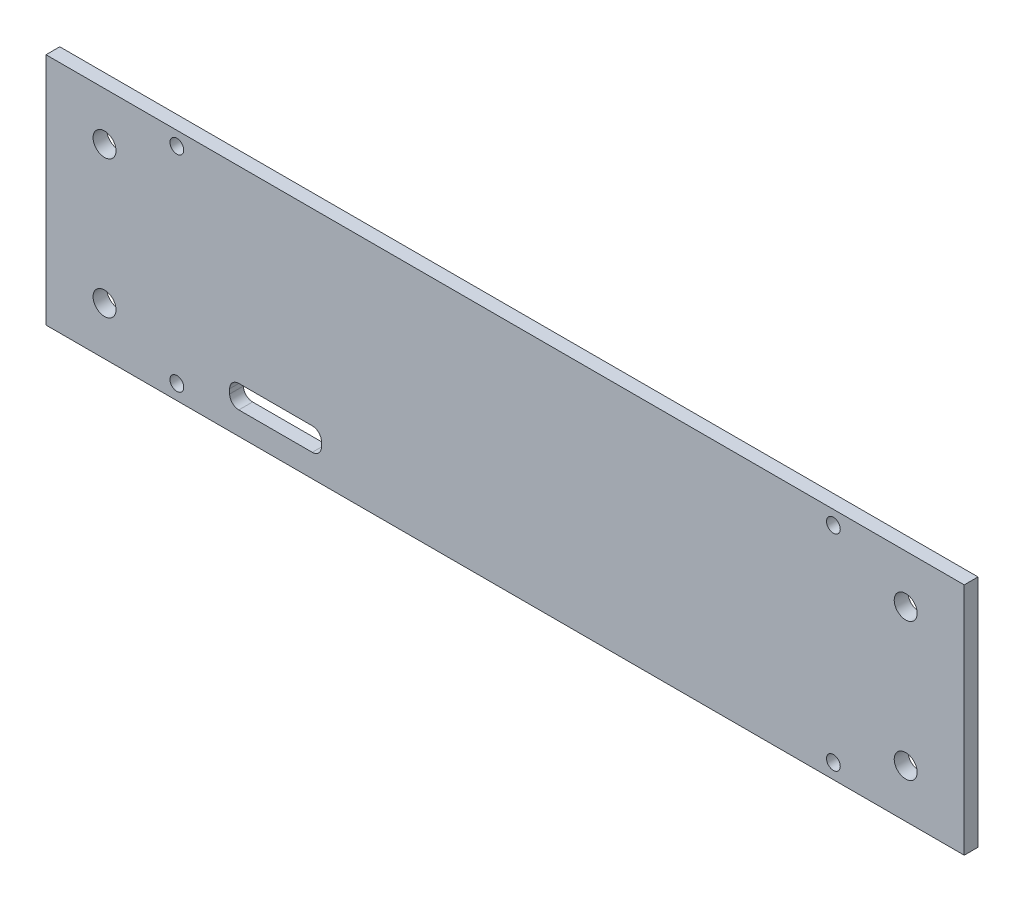
SolidWorks part; units mm, degrees
ref_plane "Front Plane" through (0, 0, 0) normal (0, 0, 1) x (1, 0, 0)
ref_plane "Top Plane" through (0, 0, 0) normal (0, 1, 0) x (1, 0, 0)
ref_plane "Right Plane" through (0, 0, 0) normal (1, 0, 0) x (0, 0, -1)
sketch "Sketch1" plane through (0, 0, 0) normal (0, 0, 1) x (1, 0, 0)
  line L1 (0, 0) -> (200, 0)
  line L2 (0, 0) -> (0, 51)
  line L3 (0, 51) -> (200, 51)
  line L4 (200, 0) -> (200, 51)
  dimension "D1" = 200
  dimension "D2" = 51
extrude "Boss-Extrude1" add sketch "Sketch1" along normal blind 3 contours L2 L1 L4 L3
sketch "Sketch2" plane through (0, 0, 3) normal (0, 0, 1) x (1, 0, 0)
  line L0 (100, 51) -> (100, 0) construction
  line L1 (0, 51) -> (200, 51) construction
  line L2 (0, 0) -> (200, 0) construction
  line L3 (28.5, 51) -> (28.5, 0) construction
  line L4 (12.75, 51) -> (12.75, 0) construction
  line L5 (0, 0) -> (0, 51) construction
  line L6 (187.25, 51) -> (187.25, 0) construction
  line L7 (171.5, 51) -> (171.5, 0) construction
  circle A0 centre (28.5, 48) radius 1.5
  circle A1 centre (28.5, 3.25) radius 1.5
  circle A2 centre (12.75, 40.5) radius 2.5
  circle A3 centre (12.75, 10.5) radius 2.5
  circle A4 centre (187.25, 40.5) radius 2.5
  circle A5 centre (187.25, 10.5) radius 2.5
  circle A6 centre (171.5, 3.25) radius 1.5
  circle A7 centre (171.5, 48) radius 1.5
  dimension "D2" = 44.75
  dimension "D3" = 3
  dimension "D5" = 30
  dimension "D6" = 5
  dimension "D7" = 10.5
  dimension "D8" = 3
  dimension "D1" = 71.5
  dimension "D4" = 12.75
extrude "Cut-Extrude1" cut sketch "Sketch2" against normal up to surface (3 mm away) up to face at (100, 25.5, 0)
sketch "Sketch3" plane through (0, 0, 3) normal (0, 0, 1) x (1, 0, 0)
  line L0 (100, 51) -> (100, 0) construction
  line L1 (0, 51) -> (200, 51) construction
  line L2 (0, 0) -> (200, 0) construction
  line L4 (40, 10) -> (60, 10)
  line L5 (40, 10) -> (40, 5)
  line L6 (40, 5) -> (60, 5)
  line L7 (60, 10) -> (60, 5)
  dimension "D1" = 20
  dimension "D2" = 5
  dimension "D3" = 40
  dimension "D4" = 5
extrude "Cut-Extrude2" cut sketch "Sketch3" against normal up to surface (3 mm away) up to face at (189.75, 40.5, 0)
fillet "Fillet1" radius 2 4 edges at (60, 10, 1.5) (60, 5, 1.5) (40, 5, 1.5) (40, 10, 1.5)
